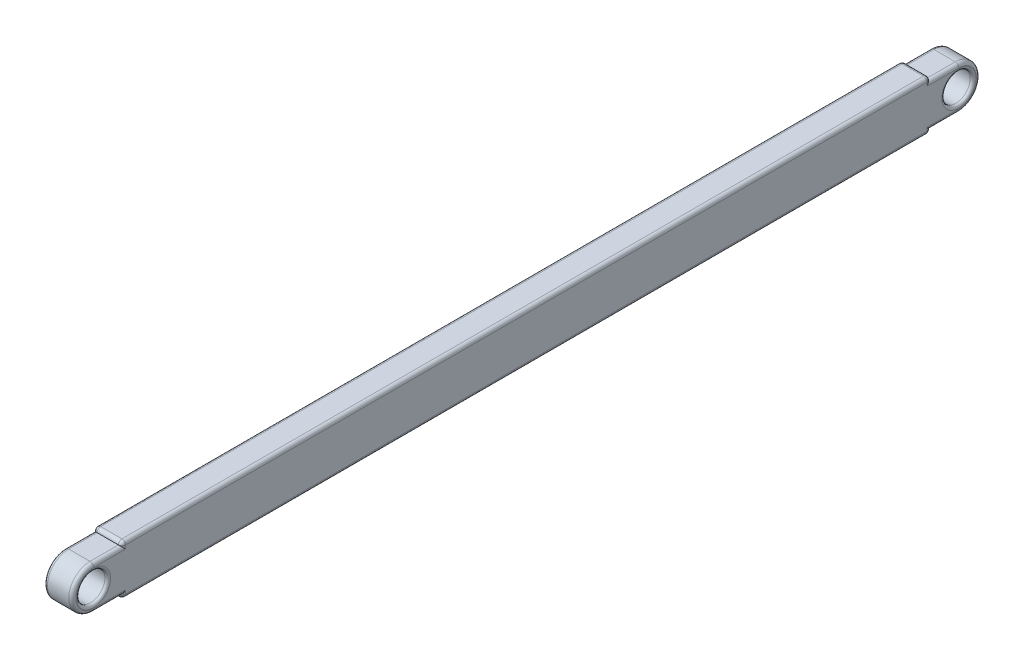
SolidWorks part; units mm, degrees
ref_plane "Front Plane" through (0, 0, 0) normal (0, 0, 1) x (1, 0, 0)
ref_plane "Top Plane" through (0, 0, 0) normal (0, 1, 0) x (1, 0, 0)
ref_plane "Right Plane" through (0, 0, 0) normal (1, 0, 0) x (0, 0, -1)
sketch "Sketch1" plane through (0, 0, 0) normal (1, 0, 0) x (0, 0, -1)
  line L0 (0, 0) -> (0, -0.125)
  line L1 (0, 0) -> (28.5, 0)
  line L2 (0, 0) -> (0, -1.75) construction
  line L3 (0, -1.75) -> (28.5, -1.75)
  line L4 (28.5, 0) -> (28.5, -1.75) construction
  line L5 (0, -0.125) -> (-1, -0.125)
  line L6 (0, -0.125) -> (0, -1.625) construction
  line L7 (0, -1.625) -> (-1, -1.625)
  line L8 (-1, -0.125) -> (-1, -1.625) construction
  line L9 (28.5, -0.125) -> (29.5, -0.125)
  line L10 (28.5, -0.125) -> (28.5, -1.625) construction
  line L11 (28.5, -1.625) -> (29.5, -1.625)
  line L12 (29.5, -0.125) -> (29.5, -1.625) construction
  line L13 (0, -1.625) -> (0, -1.75)
  line L14 (28.5, 0) -> (28.5, -0.125)
  line L15 (28.5, -1.625) -> (28.5, -1.75)
  line L16 (0, -0.875) -> (-1, -0.875) construction
  line L17 (28.5, -0.875) -> (29.5, -0.875) construction
  circle A0 centre (-1, -0.875) radius 0.5
  arc A1 (-1, -1.625) -> (-1, -0.125) centre (-1, -0.875) cw
  circle A2 centre (29.5, -0.875) radius 0.5
  arc A3 (29.5, -0.125) -> (29.5, -1.625) centre (29.5, -0.875) cw
  dimension "D1" = 1
  dimension "D4" = 1
  dimension "D2" = 1.5
  dimension "D3" = 1.5
  dimension "D5" = 30.5
  dimension "D6" = 1.75
  dimension "D7" = 1
  dimension "D8" = 1
extrude "Boss-Extrude1" add sketch "Sketch1" along normal blind 1
fillet "Fillet1" radius 0.125 16 edges at (1, -1.75, -14.25) (0, -1.75, -14.25) (0, 0, -14.25) (1, 0, -14.25) (0, -1.625, -29) (0, -0.875, -30.25) (1, -1.625, -29) (1, -0.875, -30.25) (0, -1.625, 0.5) (0, -0.875, 1.75) (1, -1.625, 0.5) (1, -0.875, 1.75) (0, -0.125, -29) (1, -0.125, -29) (0, -0.125, 0.5) (1, -0.125, 0.5)
fillet "Fillet2" radius 0.1 4 edges at (0, -0.875, 0.5) (1, -0.875, 0.5) (0, -0.875, -30) (1, -0.875, -30)
fillet "Fillet3" radius 0.125 20 edges at (1, -1.5625, 0) (0.9634, -1.7134, 0) (0.5, -1.75, 0) (0.0366, -1.7134, 0) (1, -0.1875, 0) (0.9634, -0.0366, 0) (0.5, 0, 0) (0.0366, -0.0366, 0) (1, -1.5625, -28.5) (0.9634, -1.7134, -28.5) (0.5, -1.75, -28.5) (0.0366, -1.7134, -28.5) (1, -0.1875, -28.5) (0.9634, -0.0366, -28.5) (0.5, 0, -28.5) (0.0366, -0.0366, -28.5) (0, -1.5625, 0) (0, -0.1875, 0) (0, -1.5625, -28.5) (0, -0.1875, -28.5)
